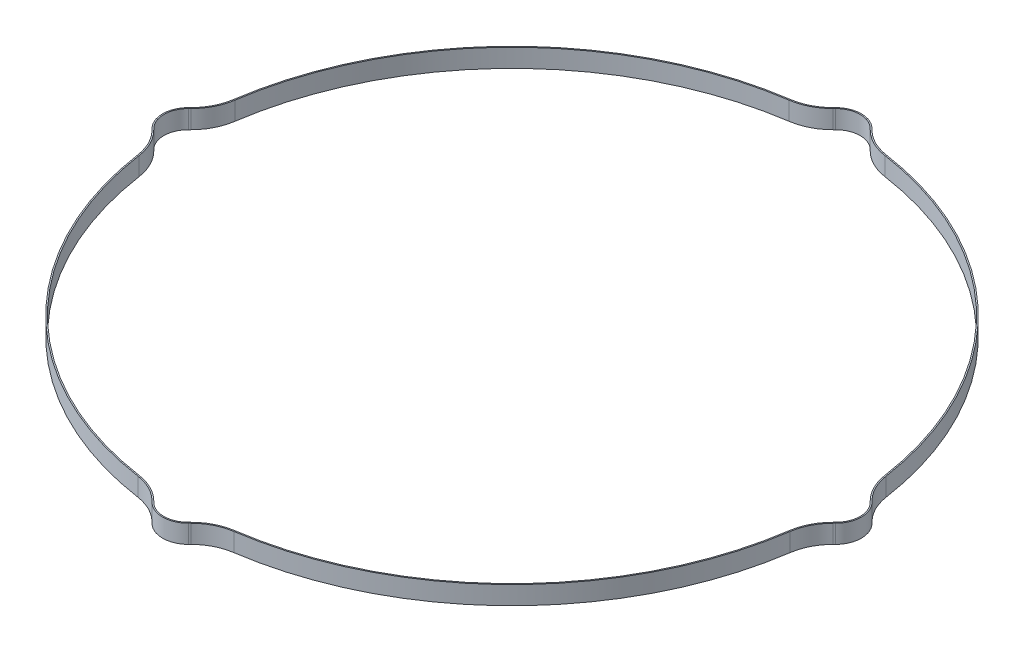
SolidWorks part; units mm, degrees
ref_plane "Front" through (0, 0, 0) normal (0, 0, 1) x (1, 0, 0)
ref_plane "Top" through (0, 0, 0) normal (0, 1, 0) x (1, 0, 0)
ref_plane "Right" through (0, 0, 0) normal (1, 0, 0) x (0, 0, -1)
sketch "Sketch1" plane through (0, 0, 0) normal (0, 1, 0) x (1, 0, 0)
  line L0 (0, 0) -> (526.4354, 0) construction
  line L5 (35.921, -708.571) -> (38.6565, -705.8356)
  line L6 (708.571, 35.921) -> (705.8356, 38.6565)
  line L7 (-35.921, 708.571) -> (-38.6565, 705.8356)
  line L8 (-708.571, -35.921) -> (-705.8356, -38.6565)
  line L9 (-38.6565, -705.8356) -> (-35.921, -708.571)
  line L10 (-705.8356, 38.6565) -> (-708.571, 35.921)
  line L11 (705.8356, -38.6565) -> (708.571, -35.921)
  line L12 (38.6565, 705.8356) -> (35.921, 708.571)
  line L13 (711.2, 0) -> (744.4921, 0) construction
  arc A0 (-99.2874, 675.3658) -> (-675.3658, 99.2874) centre (0, 0) ccw
  circle A1 centre (0, 0) radius 526.4354 construction
  arc A2 (-675.3658, -99.2874) -> (-99.2874, -675.3658) centre (0, 0) ccw
  arc A3 (99.2874, -675.3658) -> (675.3658, -99.2874) centre (0, 0) ccw
  arc A4 (675.3658, 99.2874) -> (99.2874, 675.3658) centre (0, 0) ccw
  arc A5 (35.921, 708.571) -> (-35.921, 708.571) centre (0, 672.65) ccw
  arc A6 (708.571, 35.921) -> (708.571, -35.921) centre (672.65, 0) cw
  arc A7 (-35.921, -708.571) -> (35.921, -708.571) centre (0, -672.65) ccw
  arc A8 (-708.571, 35.921) -> (-708.571, -35.921) centre (-672.65, 0) ccw
  arc A9 (-99.2874, -675.3658) -> (-38.6565, -705.8356) centre (-114.9886, -782.1678) cw
  arc A10 (99.2874, -675.3658) -> (38.6565, -705.8356) centre (114.9886, -782.1678) ccw
  arc A11 (675.3658, -99.2874) -> (705.8356, -38.6565) centre (782.1678, -114.9886) cw
  arc A12 (675.3658, 99.2874) -> (705.8356, 38.6565) centre (782.1678, 114.9886) ccw
  arc A13 (-99.2874, 675.3658) -> (-38.6565, 705.8356) centre (-114.9886, 782.1678) ccw
  arc A14 (-675.3658, 99.2874) -> (-705.8356, 38.6565) centre (-782.1678, 114.9886) cw
  arc A15 (-705.8356, -38.6565) -> (-675.3658, -99.2874) centre (-782.1678, -114.9886) cw
  arc A16 (99.2874, 675.3658) -> (38.6565, 705.8356) centre (114.9886, 782.1678) cw
  point P31 (-64.9655, -679.5266)
  point P34 (64.9655, -679.5266)
  point P37 (679.5266, -64.9655)
  point P40 (679.5266, 64.9655)
  point P48 (-679.5266, -64.9655)
  dimension "D1" = 1365.25
  dimension "D2" = 50.8
  dimension "D3" = 107.95
  dimension "D4" = 107.95
extrude "Extrude-Thin1" add sketch "Sketch1" along normal blind 38.1 thin thin type one direction wall 2.54
